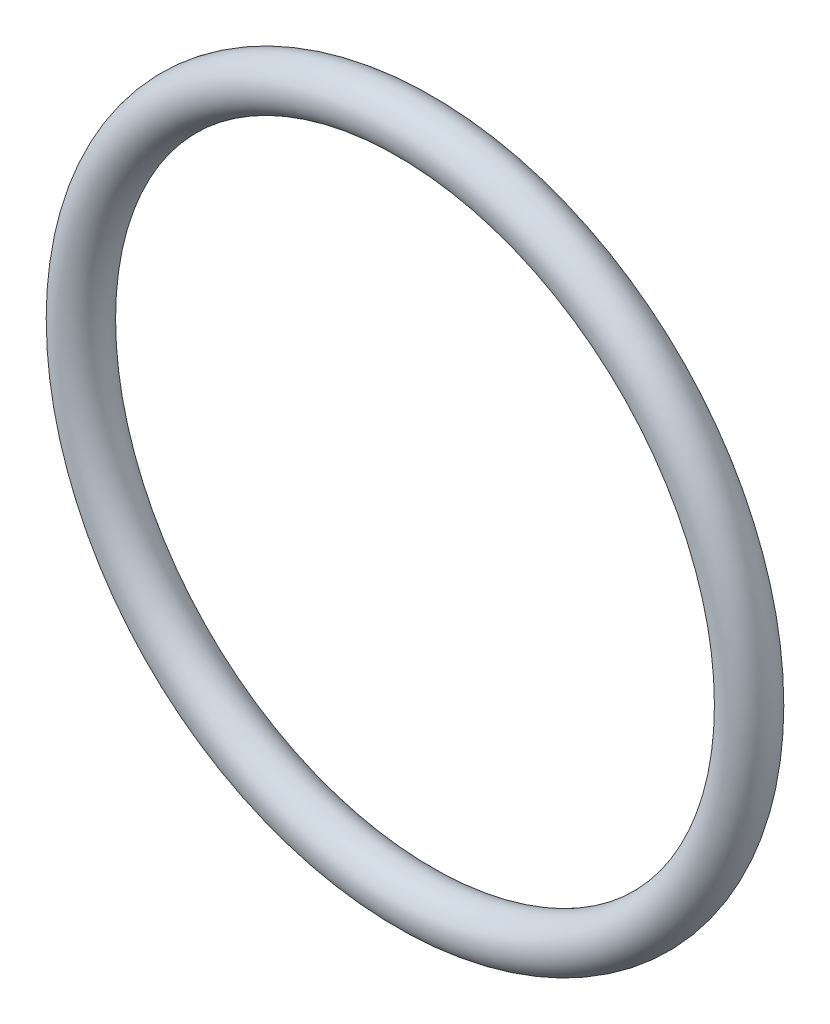
SolidWorks part; units mm, degrees
material "BUNA-N Rubber"
ref_plane "Front" through (0, 0, 0) normal (0, 0, 1) x (1, 0, 0)
ref_plane "Top" through (0, 0, 0) normal (0, 1, 0) x (1, 0, 0)
ref_plane "Right" through (0, 0, 0) normal (1, 0, 0) x (0, 0, -1)
sketch "Sketch1" plane through (0, 0, 0) normal (1, 0, 0) x (0, -1, 0)
  line L0 (0, -1.3081) -> (0, 1.3081) construction
  line L2 (-21.0248, 0) -> (21.0248, 0) construction
  line L3 (-16.4973, 0) -> (16.4973, 0) construction
  circle A0 centre (17.8054, 0) radius 1.3081
  point P9 (16.4973, 0)
  point P10 (19.1135, 0)
  point P13 (17.8054, 1.3081)
  point P14 (17.8054, -1.3081)
  dimension "Width" = 2.6162
  dimension "ID" = 32.9946
revolve "Revolve1" add sketch "Sketch1" angle 360 about L0
ref_axis "Axis1" through (0, 0, -1.4389) along (0, 0, 1)
